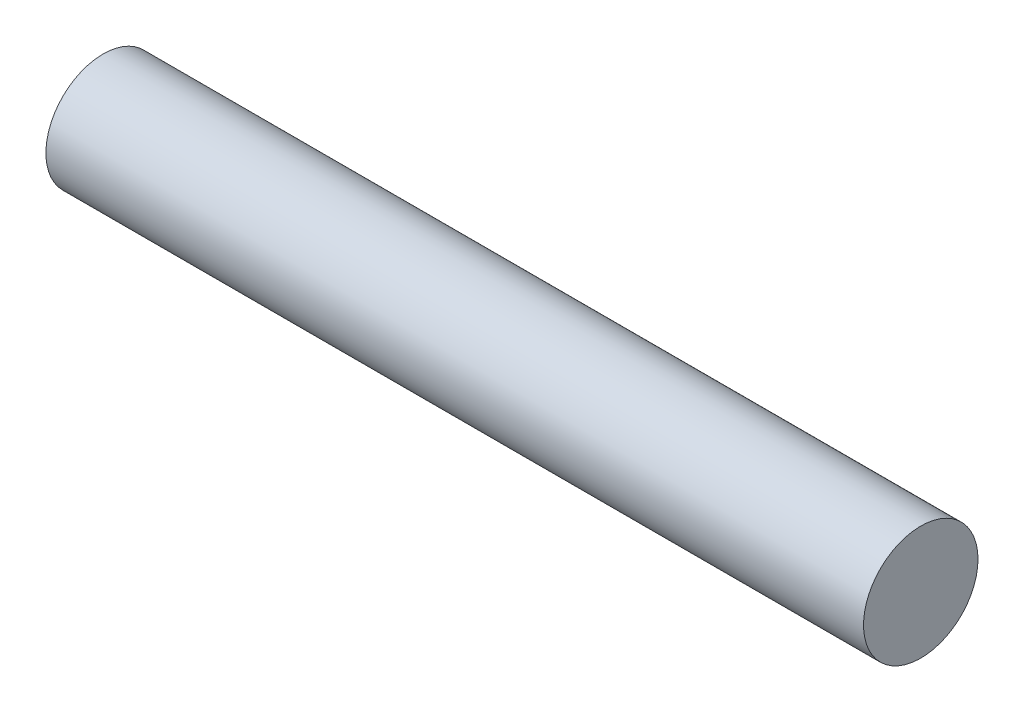
SolidWorks part; units mm, degrees
ref_plane "Front" through (0, 0, 0) normal (0, 0, 1) x (1, 0, 0)
ref_plane "Top" through (0, 0, 0) normal (0, 1, 0) x (1, 0, 0)
ref_plane "Right" through (0, 0, 0) normal (1, 0, 0) x (0, 0, -1)
sketch "Sketch1" plane through (0, 0, 0) normal (1, 0, 0) x (0, 0, -1)
  circle A0 centre (0, 0) radius 21
extrude "Base" add sketch "Sketch1" along normal blind 300
cosmetic thread "ThreadCosmetic1" [suppressed] parameters "D2"=38.752
sketch "Sketch2" plane through (0, 0, 0) normal (0, 0, 1) x (1, 0, 0)
  line L0 (300, 19.5936) -> (300.812, 21)
  line L1 (300.812, 21) -> (300.812, 21.5)
  line L2 (300.812, 21.5) -> (299.188, 21.5)
  line L3 (299.188, 21.5) -> (299.188, 21)
  line L4 (299.188, 21) -> (300, 19.5936)
  line L5 (0, 0) -> (325.0946, 0) construction
  line L6 (300, -21) -> (300, 21) construction
  dimension "D1" = 60
  dimension "D2" = 60
  dimension "D3" = 0.5
  dimension "D4" = 1.624
  dimension "D5" = 42
revolve "Cut-Revolve10" [suppressed] cut sketch "Sketch2" angle 360 about L5
pattern_linear "LPattern10" [suppressed] count 15 spacing 19.488 along (-1, 0, 0) of bodies 102
equation "\"D5@Sketch2\" = \"d@Sketch1\""
equation "\"D4@Sketch2\" = (  \"d@Sketch1\" - \"D2@ThreadCosmetic1\" )  / 2"
equation "\"D3@LPattern10\" = \"D4@Sketch2\" * 1.2 * 10"
equation "\"D1@LPattern10\" = \"l@Base\" / \"D3@LPattern10\""
